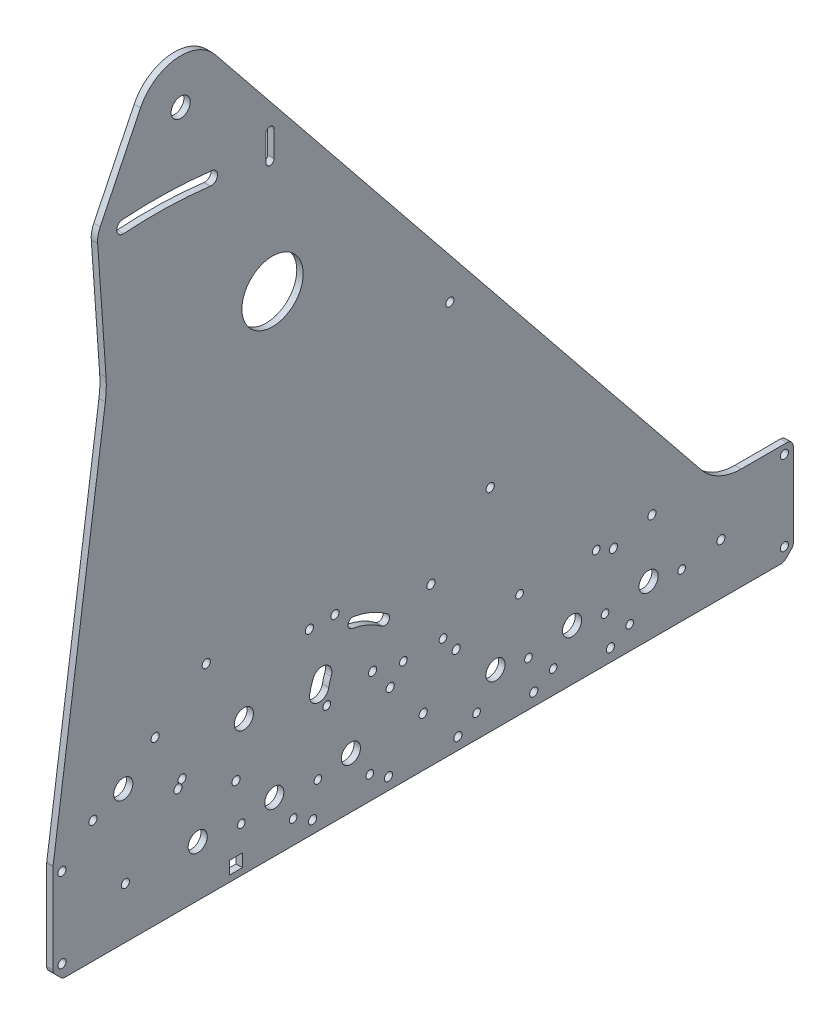
SolidWorks part; units mm, degrees
ref_plane "Front Plane" through (0, 0, 0) normal (0, 0, 1) x (1, 0, 0)
ref_plane "Top Plane" through (0, 0, 0) normal (0, 1, 0) x (1, 0, 0)
ref_plane "Right Plane" through (0, 0, 0) normal (1, 0, 0) x (0, 0, -1)
sketch "Sketch1" plane through (0, 0, 0) normal (1, 0, 0) x (0, 0, -1)
  line L0 (-184.15, -24.6062) -> (184.15, -24.6062)
  line L1 (184.15, -24.6062) -> (184.15, 26.1938)
  line L2 (184.15, 26.1938) -> (146.05, 26.1937)
  line L5 (-142.6632, 324.5299) -> (-184.15, 26.1938)
  line L6 (-184.15, 26.1938) -> (-184.15, -24.6062)
  line L7 (-184.15, 350.0437) -> (184.15, 350.0437) construction
  line L9 (146.05, 26.1937) -> (-103.3504, 335.4213)
  arc A0 (-103.3504, 335.4213) -> (-142.6632, 324.5299) centre (-120.65, 321.4687) ccw
  point P8 (0, -24.6062)
  dimension "D1" = 368.3
  dimension "D7" = 44.45
  dimension "D2" = 50.8
  dimension "D3" = 38.1
  dimension "D4" = 24.6062
  dimension "D5" = 374.65
  dimension "D6" = 304.8
  dimension "D8" = 346.075
extrude "Boss-Extrude1" add sketch "Sketch1" along normal blind 3.175
chamfer "Chamfer1" distance 4.7625 angle 45 2 edges at (1.5875, -24.6062, 184.15) (1.5875, -24.6062, -184.15)
fillet "Fillet1" radius 25.4 1 edges at (1.5875, 26.1937, -146.05)
fillet "Fillet2" radius 3.175 2 edges at (1.5875, 26.1938, 184.15) (1.5875, 26.1938, -184.15)
fillet "Fillet3" radius 3.175 4 edges at (1.5875, -19.8438, -184.15) (1.5875, -24.6062, -179.3875) (1.5875, -19.8437, 184.15) (1.5875, -24.6062, 179.3875)
sketch "Sketch30" plane through (3.175, 0, 0) normal (1, 0, 0) x (0, 0, -1)
  circle A8 centre (-89.211, 42.2593) radius 4.7625
  circle A9 centre (-25.1593, 30.6938) radius 2.032
  arc A10 (-51.7173, 35.4892) -> (-50.2741, 40.5715) centre (-25.1593, 30.6938) cw construction
  arc A11 (-54.7652, 42.3379) -> (-56.4665, 36.3468) centre (-25.1593, 30.6938) ccw
  arc A12 (-45.783, 38.8051) -> (-46.9681, 34.6317) centre (-25.1593, 30.6938) ccw
  arc A13 (-45.783, 38.8051) -> (-54.7652, 42.3379) centre (-50.2741, 40.5715) ccw
  arc A14 (-56.4665, 36.3468) -> (-46.9681, 34.6317) centre (-51.7173, 35.4892) ccw
  arc A15 (-34.9881, 56.6661) -> (-19.1131, 49.8125) centre (-41.7582, 19.1724) cw construction
  arc A16 (-17.6789, 51.753) -> (-34.5594, 59.0407) centre (-41.7582, 19.1724) ccw
  arc A17 (-20.5473, 47.8719) -> (-35.4169, 54.2915) centre (-41.7582, 19.1724) ccw
  arc A18 (-20.5473, 47.8719) -> (-17.6789, 51.753) centre (-19.1131, 49.8125) ccw
  arc A19 (-34.5594, 59.0407) -> (-35.4169, 54.2915) centre (-34.9881, 56.6661) ccw
  arc A20 (-19.1131, 49.8125) -> (-34.9881, 56.6661) centre (-41.7582, 19.1724) ccw construction
  circle A21 centre (94.6345, 23.8125) radius 2.032
  circle A22 centre (-56.6241, 64.5541) radius 2.032
  circle A23 centre (-43.9241, 64.5541) radius 2.032
  circle A24 centre (-56.6241, 64.5541) radius 1.905 construction
  circle A25 centre (-43.9241, 64.5541) radius 1.905 construction
  point P7 (-51.1204, 38.0658)
  point P19 (-26.6567, 54.1518)
  dimension "D2" = 9.652
  dimension "D4" = 4.064
  dimension "D1" = 4.064
  dimension ".375" = 9.525
  dimension "D3" = 4.826
extrude "Cut-Extrude9" cut sketch "Sketch30" against normal through all
sketch "Sketch16" plane through (3.175, 0, 0) normal (1, 0, 0) x (0, 0, -1)
  circle A0 centre (112.1746, 0.7937) radius 4.7625
  circle A1 centre (74.0746, 0.7937) radius 4.7625
  circle A2 centre (35.9746, 0.7937) radius 4.7625
  circle A3 centre (-35.9746, 0.7938) radius 4.7625
  circle A4 centre (-74.0746, 0.7938) radius 4.7625
  circle A5 centre (-112.1746, 0.7937) radius 4.7625
  dimension "D1" = 9.525
  dimension "D2" = 9.525
extrude "Cut-Extrude1" cut sketch "Sketch16" against normal up to next
sketch "Sketch25" plane through (3.175, 0, 0) normal (1, 0, 0) x (0, 0, -1)
  circle A0 centre (102.7672, -13.0003) radius 1.905 construction
  circle A1 centre (86.0486, 27.3622) radius 1.905 construction
  circle A2 centre (128.5804, -2.3081) radius 1.905 construction
  circle A3 centre (102.7672, -13.0003) radius 1.905
  circle A4 centre (86.0486, 27.3622) radius 1.905
  circle A5 centre (128.5804, -2.3081) radius 1.905
  circle A6 centre (64.6672, -13.0003) radius 1.905 construction
  circle A8 centre (-9.8486, 27.3622) radius 1.905 construction
  circle A10 centre (-47.9486, 27.3622) radius 1.905 construction
  circle A11 centre (-90.4804, -2.3081) radius 1.905 construction
  circle A12 centre (-64.6672, -13.0003) radius 1.905 construction
  circle A14 centre (-52.3804, -2.3081) radius 1.905 construction
  circle A15 centre (-26.5672, -13.0003) radius 1.905 construction
  circle A16 centre (9.8486, 27.3622) radius 1.905 construction
  circle A17 centre (26.5672, -13.0003) radius 1.905 construction
  circle A18 centre (47.9486, 27.3622) radius 1.905 construction
  circle A19 centre (52.3804, -2.3081) radius 1.905 construction
  circle A20 centre (90.4804, -2.3081) radius 1.905 construction
  circle A21 centre (-9.8486, 27.3622) radius 1.905
  circle A23 centre (-47.9486, 27.3622) radius 1.905
  circle A24 centre (-90.4804, -2.3081) radius 1.905
  circle A25 centre (-64.6672, -13.0003) radius 1.905
  circle A27 centre (-52.3804, -2.3081) radius 1.905
  circle A28 centre (-26.5672, -13.0003) radius 1.905
  circle A29 centre (9.8486, 27.3622) radius 1.905
  circle A30 centre (26.5672, -13.0003) radius 1.905
  circle A31 centre (47.9486, 27.3622) radius 1.905
  circle A32 centre (64.6672, -13.0003) radius 1.905
  circle A33 centre (52.3804, -2.3081) radius 1.905
  circle A34 centre (90.4804, -2.3081) radius 1.905
extrude "Cut-Extrude4" cut sketch "Sketch25" against normal up to next
sketch "Sketch23" plane through (3.175, 0, 0) normal (1, 0, 0) x (0, 0, -1)
  circle A0 centre (179.705, 21.7488) radius 1.905 construction
  point P0 (-55.0246, -18.3223)
  point P6 (-93.1246, 17.5943)
  point P9 (-17.2515, -18.6426)
  point P12 (-16.4124, 19.3854)
  point P15 (16.4124, 19.3854)
  point P18 (17.2515, -18.6426)
  point P21 (55.0246, -18.3223)
  point P35 (3.8736, 53.6853)
  point P38 (113.7728, 28.6594)
  point P44 (-179.705, 21.7487)
  point P47 (-179.705, -18.0026)
  point P50 (179.705, 21.7488)
  point P53 (179.705, -18.0026)
  point P59 (93.1246, -18.3223)
  point P63 (-122.0103, 28.5049)
  point P66 (-164.29, 36.0603)
hole_wizard "#8 (0.16) Diameter Hole1" positions "Sketch23" profile "Sketch24" hole size "#8" standard "ANSI Inch" end condition up to next
sketch "Sketch24" plane through (3.175, -18.3223, 55.0246) normal (0, 1, 0) x (0, 0, -1)
  line L0 (0, 0) -> (0, 3.175)
  line L1 (0, 3.175) -> (2.032, 3.175)
  line L2 (2.032, 3.175) -> (2.032, 0)
  line L5 (2.032, 0) -> (0, 0)
  line L11 (0, -6.35) -> (0, 107.95) construction
  dimension "Thru Hole Dia." = 4.064
  dimension "Thru Hole Depth" = 3.175
sketch "Sketch22" plane through (3.175, 0, 0) normal (1, 0, 0) x (0, 0, -1)
  line L0 (-96.2996, -15.1473) -> (-89.9496, -15.1473) construction
  line L1 (-96.2996, -15.1473) -> (-89.9496, -15.1473)
  line L2 (-96.2996, -15.1473) -> (-96.2996, -21.4973)
  line L3 (-96.2996, -21.4973) -> (-89.9496, -21.4973)
  line L4 (-89.9496, -15.1473) -> (-89.9496, -21.4973)
  line L5 (-96.2996, -15.1473) -> (-89.9496, -21.4973) construction
  line L6 (-96.2996, -21.4973) -> (-89.9496, -15.1473) construction
  line L7 (-89.9496, -15.1473) -> (-89.9496, -19.8734) construction
  point P0 (-93.1246, -18.3223)
  dimension "D1" = 6.35
extrude "Cut-Extrude3" cut sketch "Sketch22" against normal up to next
sketch "Sketch21" plane through (3.175, 0, 0) normal (1, 0, 0) x (0, 0, -1)
  circle A0 centre (-148.1579, 0.7937) radius 2.032
  circle A2 centre (0, 0) radius 2.032
  circle A3 centre (148.1579, 0.7938) radius 2.032
  dimension "D1" = 4.064
extrude "Cut-Extrude2" cut sketch "Sketch21" against normal up to next
sketch "Sketch26" [suppressed] plane through (3.175, 0, 0) normal (1, 0, 0) x (0, 0, -1)
  line L0 (-145.839, 321.5609) -> (-184.1236, 26.3971) construction
  line L1 (-178.0724, -24.6062) -> (178.0724, -24.6062) construction
  circle A0 centre (-121.0218, 216.6937) radius 15.24
  dimension "D1" = 30.48
  dimension "D2" = 38.1
  dimension "D3" = 241.3
extrude "Cut-Extrude5" [suppressed] cut sketch "Sketch26" against normal through all
sketch "Sketch27" plane through (3.175, 0, 0) normal (1, 0, 0) x (0, 0, -1)
  circle A0 centre (-120.65, 321.4687) radius 4.7625
  dimension "D1" = 9.525
extrude "Cut-Extrude6" cut sketch "Sketch27" against normal through all
sketch "Sketch28" plane through (3.175, 0, 0) normal (1, 0, 0) x (0, 0, -1)
  line L0 (-120.65, 321.4687) -> (-103.9389, 280.2796) construction
  line L1 (-103.9389, 280.2796) -> (-86.9156, 261.4285) construction
  line L2 (-86.9156, 261.4285) -> (-90.8226, 249.3444) construction
  line L3 (-90.8226, 249.3444) -> (-94.7296, 237.2603) construction
  line L4 (-142.6632, 324.5299) -> (-184.1197, 26.4114) construction
  circle A0 centre (-94.7296, 237.2603) radius 2.032
  circle A1 centre (-90.8226, 249.3444) radius 2.032
  circle A2 centre (-86.9156, 261.4285) radius 2.0955
  circle A3 centre (-103.9389, 280.2796) radius 2.032
  dimension "D4" = 4.064
  dimension "D5" = 4.191
  dimension "D6" = 4.064
  dimension "D1" = 25.4
  dimension "D2" = 44.45
  dimension "D3" = 12.7
  dimension "D7" = 30
  dimension "D8" = 120
  dimension "D9" = 160
extrude "Cut-Extrude7" [suppressed] cut sketch "Sketch28" against normal through all
sketch "Sketch29" plane through (3.175, 0, 0) normal (1, 0, 0) x (0, 0, -1)
  line L1 (-76.2, 288.925) -> (-76.2, 276.225) construction
  line L2 (-74.168, 288.925) -> (-74.168, 276.225)
  line L3 (-78.232, 288.925) -> (-78.232, 276.225)
  arc A4 (-74.168, 288.925) -> (-78.232, 288.925) centre (-76.2, 288.925) ccw
  arc A5 (-78.232, 276.225) -> (-74.168, 276.225) centre (-76.2, 276.225) ccw
  point P8 (-76.2, 282.575)
  dimension "D1" = 276.225
  dimension "D2" = 2.032
  dimension "D3" = 76.2
  dimension "D4" = 12.7
sketch "Sketch31" plane through (0, 0, 0) normal (-1, 0, 0) x (0, 0, 1)
extrude "Cut-Extrude10" [suppressed] cut sketch "Sketch31" against normal through all
sketch "Sketch34" plane through (0, 0, 0) normal (-1, 0, 0) x (0, 0, 1)
  line L3 (123.2042, 95.6381) -> (126.7027, 70.4802) construction
  line L4 (125.3426, 95.9355) -> (128.8411, 70.7775)
  line L5 (121.0658, 95.3407) -> (124.5642, 70.1828)
  line L6 (142.6632, 324.5299) -> (184.1197, 26.4114) construction
  arc A2 (125.3426, 95.9355) -> (121.0658, 95.3407) centre (123.2042, 95.6381) ccw
  arc A3 (124.5642, 70.1828) -> (128.8411, 70.7775) centre (126.7027, 70.4802) ccw
  point P9 (124.9534, 83.0591)
  dimension "D8" = 4.318
  dimension "D6" = 50.8
  dimension "D7" = 25.4
extrude "Cut-Extrude12" [suppressed] cut sketch "Sketch34" against normal through all
sketch "Sketch38" plane through (3.175, 0, 0) normal (1, 0, 0) x (0, 0, -1)
  line L0 (-184.15, 25.974) -> (-184.15, -18.5286) construction
  line L1 (-178.0724, -24.6062) -> (178.0724, -24.6062) construction
  circle A0 centre (-133.35, 56.3562) radius 2.032
  circle A1 centre (-149.225, 42.0687) radius 4.7625
  circle A2 centre (-107.95, 75.4062) radius 2.032
  dimension "D1" = 50.8
  dimension "D3" = 4.064
  dimension "D4" = 9.525
  dimension "D7" = 4.064
  dimension "D2" = 80.9625
  dimension "D5" = 15.875
  dimension "D6" = 14.2875
  dimension "D8" = 25.4
  dimension "D9" = 19.05
extrude "Cut-Extrude14" cut sketch "Sketch38" against normal through all
sketch "Sketch37" plane through (3.175, 0, 0) normal (1, 0, 0) x (0, 0, -1)
  circle A0 centre (33.3375, 80.645) radius 2.032
  circle A8 centre (0, 0) radius 2.032 construction
  dimension "D1" = 4.064
  dimension "D2" = 33.3375
  dimension "D3" = 80.645
extrude "Cut-Extrude13" cut sketch "Sketch37" against normal through all
extrude "Cut-Extrude15" cut sketch "Sketch29" against normal through all
sketch "Sketch40" plane through (3.175, 0, 0) normal (1, 0, 0) x (0, 0, -1)
  circle A0 centre (-120.015, 31.75) radius 2.032
  dimension "D1" = 4.064
  dimension "D2" = 120.015
  dimension "D3" = 31.75
extrude "Cut-Extrude16" cut sketch "Sketch40" against normal through all
sketch "Sketch41" [suppressed] plane through (3.175, 0, 0) normal (1, 0, 0) x (0, 0, -1)
  line L0 (-120.65, 318.2937) -> (-98.425, 279.7989) construction
  line L1 (-98.425, 279.7989) -> (-77.6666, 265.1617) construction
  line L2 (-120.65, 318.2937) -> (-60.41, 318.2937) construction
  circle A0 centre (-120.65, 318.2937) radius 25.4 construction
  circle A1 centre (-98.425, 279.7989) radius 19.05 construction
  circle A2 centre (-77.6666, 265.1617) radius 6.35 construction
  circle A3 centre (-98.425, 279.7989) radius 2.032
  circle A4 centre (-77.6666, 265.1617) radius 2.032
  dimension "D1" = 50.8
  dimension "D2" = 38.1
  dimension "D3" = 12.7
  dimension "D4" = 4.064
  dimension "D5" = 60
extrude "Cut-Extrude17" [suppressed] cut sketch "Sketch41" against normal through all
sketch "Sketch43" plane through (3.175, 0, 0) normal (1, 0, 0) x (0, 0, -1)
  line L0 (-152.4, 200.025) -> (-123.6487, 200.025) construction
  line L1 (-115.9779, 252.0412) -> (-152.4, 200.025) construction
  circle A0 centre (-152.4, 200.025) radius 2.032
  arc A1 (-143.2813, 262.8669) -> (-96.4668, 230.087) centre (-152.4, 200.025) cw construction
  arc A2 (-92.2158, 232.3717) -> (-142.5883, 267.6428) centre (-152.4, 200.025) ccw
  arc A3 (-100.7177, 227.8023) -> (-143.9743, 258.0909) centre (-152.4, 200.025) ccw
  arc A4 (-100.7177, 227.8023) -> (-92.2158, 232.3717) centre (-96.4668, 230.087) ccw
  arc A5 (-142.5883, 267.6428) -> (-143.9743, 258.0909) centre (-143.2813, 262.8669) ccw
  point P6 (-115.9779, 252.0412)
  dimension "D1" = 4.064
  dimension "D4" = 4.826
  dimension "D2" = 200.025
  dimension "D3" = 152.4
  dimension "D5" = 63.5
  dimension "D6" = 57.15
  dimension "D7" = 55
extrude "Cut-Extrude19" [suppressed] cut sketch "Sketch43" against normal through all
sketch "Sketch44" plane through (3.175, 0, 0) normal (1, 0, 0) x (0, 0, -1)
  circle A0 centre (-142.875, 226.3775) radius 2.032
  dimension "D1" = 4.064
  dimension "D2" = 142.875
  dimension "D3" = 226.3775
extrude "Cut-Extrude20" [suppressed] cut sketch "Sketch44" against normal through all
sketch "Sketch50" plane through (0, 0, 0) normal (-1, 0, 0) x (0, 0, 1)
  line L0 (89.6567, 207.1688) -> (64.2567, 207.1688) construction
  line L1 (89.6567, 205.1368) -> (64.2567, 205.1368)
  line L2 (89.6567, 209.2008) -> (64.2567, 209.2008)
  line L3 (64.2567, 194.4688) -> (38.8567, 194.4688) construction
  line L4 (64.2567, 192.4368) -> (38.8567, 192.4368)
  line L5 (64.2567, 196.5008) -> (38.8567, 196.5008)
  arc A1 (89.6567, 205.1368) -> (89.6567, 209.2008) centre (89.6567, 207.1688) ccw
  arc A2 (64.2567, 209.2008) -> (64.2567, 205.1368) centre (64.2567, 207.1688) ccw
  arc A3 (64.2567, 192.4368) -> (64.2567, 196.5008) centre (64.2567, 194.4688) ccw
  arc A4 (38.8567, 196.5008) -> (38.8567, 192.4368) centre (38.8567, 194.4688) ccw
  point P3 (76.9567, 207.1688)
  point P5 (51.5567, 194.4688)
  dimension "D1" = 2.032
  dimension "D2" = 207.1688
  dimension "D3" = 89.6567
  dimension "D4" = 25.4
  dimension "D5" = 12.7
extrude "Cut-Extrude22" [suppressed] cut sketch "Sketch50" against normal through all
sketch "Sketch51" plane through (3.175, 0, 0) normal (1, 0, 0) x (0, 0, -1)
  circle A0 centre (-111.125, 222.6469) radius 2.032
  circle A1 centre (-111.125, 190.8969) radius 2.032
  dimension "D1" = 222.6469
  dimension "D3" = 31.75
  dimension "D4" = 4.064
  dimension "D2" = 111.125
extrude "Cut-Extrude23" [suppressed] cut sketch "Sketch51" against normal through all
sketch "Sketch52" [suppressed] plane through (0, 0, 0) normal (-1, 0, 0) x (0, 0, 1)
  line L0 (145.839, 321.5609) -> (184.1236, 26.3971) construction
  line L1 (142.875, 226.3775) -> (142.0856, 251.7652) construction
  line L2 (120.4939, 238.3877) -> (142.875, 226.3775) construction
  arc A5 (142.0856, 251.7652) -> (120.4939, 238.3877) centre (142.875, 226.3775) ccw construction
  arc A6 (142.0224, 253.7962) -> (118.7034, 239.3485) centre (142.875, 226.3775) ccw
  arc A7 (142.1487, 249.7342) -> (122.2844, 237.4269) centre (142.875, 226.3775) ccw
  arc A8 (142.1487, 249.7342) -> (142.0224, 253.7962) centre (142.0856, 251.7652) ccw
  arc A9 (118.7034, 239.3485) -> (122.2844, 237.4269) centre (120.4939, 238.3877) ccw
  point P4 (129.4975, 247.9692)
  dimension "D1" = 25.4
  dimension "D2" = 2.032
  dimension "D3" = 12.7
  dimension "D4" = 60
extrude "Cut-Extrude24" [suppressed] cut sketch "Sketch52" against normal through all
sketch "Sketch53" plane through (3.175, 0, 0) normal (1, 0, 0) x (0, 0, -1)
  line L0 (-25.4, 197.2663) -> (-25.4, 135.876) construction
  line L1 (-23.368, 197.2663) -> (-23.368, 135.876)
  line L2 (-27.432, 197.2663) -> (-27.432, 135.876)
  arc A0 (-23.368, 197.2663) -> (-27.432, 197.2663) centre (-25.4, 197.2663) ccw
  arc A1 (-27.432, 135.876) -> (-23.368, 135.876) centre (-25.4, 135.876) ccw
  point P2 (-25.4, 166.5712)
  dimension "D1" = 2.032
  dimension "D2" = 61.3903
  dimension "D3" = 197.2663
  dimension "D4" = 25.4
extrude "Cut-Extrude25" [suppressed] cut sketch "Sketch53" against normal through all
sketch "Sketch56" plane through (3.175, 0, 0) normal (1, 0, 0) x (0, 0, -1)
  line L0 (-133.35, 284.9563) -> (-133.35, 56.3562) construction
  line L1 (-149.2963, 284.3994) -> (-133.35, 56.3562) construction
  line L2 (-133.35, 56.3562) -> (-105.4907, 283.2523) construction
  arc A0 (-149.2963, 284.3994) -> (-105.4907, 283.2523) centre (-133.35, 56.3562) cw
  arc A1 (-142.7671, 191.0274) -> (-116.8976, 190.35) centre (-133.35, 56.3562) cw
  dimension "D1" = 4
  dimension "D3" = 228.6
  dimension "D4" = 135
  dimension "D2" = 7
sketch "Sketch54" plane through (3.175, 0, 0) normal (1, 0, 0) x (0, 0, -1)
  line L0 (-142.6632, 324.5299) -> (-184.1197, 26.4114) construction
  line L1 (-140.6316, 331.1994) -> (-160.7144, 289.9597)
  line L2 (-142.6632, 324.5299) -> (-157.4154, 218.4453)
  line L3 (-140.6316, 331.1994) -> (-217.348, 331.1994) construction
  line L4 (-149.2963, 284.3994) -> (-133.35, 56.3562) construction
  line L5 (-161.9654, 283.5135) -> (-157.4154, 218.4453)
  arc A1 (-103.3504, 335.4213) -> (-142.6632, 324.5299) centre (-120.65, 321.4687) ccw construction
  arc A2 (-160.7144, 289.9597) -> (-161.9654, 283.5135) centre (-149.2963, 284.3994) ccw
  arc A3 (-140.6316, 331.1994) -> (-142.6632, 324.5299) centre (-120.65, 321.4687) ccw
  dimension "D1" = 12.7
extrude "Boss-Extrude2" add sketch "Sketch54" against normal up to surface (3.175 mm away) up to face at (0, 282.575, 76.2)
sketch "Sketch57" plane through (3.175, 0, 0) normal (1, 0, 0) x (0, 0, -1)
  line L0 (138.4249, 35.6479) -> (-103.3504, 335.4213) construction
  arc A0 (-149.2963, 284.3994) -> (-105.4907, 283.2523) centre (-133.35, 56.3562) cw construction
  arc A1 (-105.1037, 286.4036) -> (-149.5178, 287.5667) centre (-133.35, 56.3562) ccw
  arc A2 (-105.8776, 280.101) -> (-149.0749, 281.2321) centre (-133.35, 56.3562) ccw
  arc A3 (-105.8776, 280.101) -> (-105.1037, 286.4036) centre (-105.4907, 283.2523) ccw
  arc A4 (-149.5178, 287.5667) -> (-149.0749, 281.2321) centre (-149.2963, 284.3994) ccw
  arc A5 (-105.4907, 283.2523) -> (-149.2963, 284.3994) centre (-133.35, 56.3562) ccw construction
  arc A6 (-142.7671, 191.0274) -> (-116.8976, 190.35) centre (-133.35, 56.3562) cw construction
  arc A7 (-116.5107, 193.5013) -> (-142.9886, 194.1947) centre (-133.35, 56.3562) ccw construction
  arc A8 (-117.2846, 187.1986) -> (-142.5456, 187.8601) centre (-133.35, 56.3562) ccw construction
  arc A9 (-117.2846, 187.1986) -> (-116.5107, 193.5013) centre (-116.8976, 190.35) ccw construction
  arc A10 (-142.9886, 194.1947) -> (-142.5456, 187.8601) centre (-142.7671, 191.0274) ccw construction
  circle A11 centre (13.2774, 170.5867) radius 2.032
  point P3 (-127.3659, 284.8779)
  point P16 (-129.8161, 191.31)
  dimension "D1" = 6.35
  dimension "D2" = 4.064
  dimension "D3" = 12.7
  dimension "D4" = 130.175
extrude "Cut-Extrude26" cut sketch "Sketch57" against normal up to next
sketch "Sketch58" plane through (3.175, 0, 0) normal (1, 0, 0) x (0, 0, -1)
  line L0 (138.4249, 35.6479) -> (-103.3504, 335.4213) construction
  line L1 (-74.9571, 219.298) -> (-112.7732, 223.9412) construction
  line L2 (-133.35, 56.3562) -> (-105.4907, 283.2523) construction
  circle A0 centre (-74.9571, 219.298) radius 15.24
  dimension "D1" = 50.8
  dimension "D2" = 30.48
  dimension "D3" = 38.1
extrude "Cut-Extrude27" cut sketch "Sketch58" against normal through all
sketch "Sketch60" [suppressed] plane through (0, 0, 0) normal (-1, 0, 0) x (0, 0, 1)
  line L1 (-40.2733, 127) -> (106.3603, 186.4422) construction
  line L2 (120.65, 321.4687) -> (120.65, 283.4951) construction
  line L3 (-40.2733, 127) -> (67.2673, 265.0656) construction
  line L4 (109.8203, 191.9056) -> (104.0156, 294.388) construction
  line L5 (69.0152, 266.5427) -> (112.1985, 289.8108) construction
  line L6 (-138.4249, 35.6479) -> (103.3504, 335.4213) construction
  line L7 (120.65, 321.4687) -> (120.65, 359.4144) construction
  line L8 (120.65, 321.4687) -> (109.5629, 294.7022) construction
  line L10 (120.65, 321.4687) -> (-169.232, 227.2804) construction
  line L11 (120.65, 321.4687) -> (354.1403, 125.5471) construction
  circle A7 centre (74.8099, 220.4974) radius 33.3375 construction
  circle A10 centre (71.6507, 261.6513) radius 2.032
  circle A11 centre (71.6507, 261.6513) radius 7.9375 construction
  circle A12 centre (104.2729, 191.5914) radius 2.032
  circle A14 centre (104.2729, 191.5914) radius 7.9375 construction
  circle A15 centre (-40.2733, 127) radius 2.032
  circle A16 centre (104.2729, 191.5914) radius 5.5563 construction
  circle A17 centre (120.65, 321.4687) radius 22.225 construction
  circle A20 centre (109.5629, 294.7022) radius 6.7469 construction
  circle A21 centre (109.5629, 294.7022) radius 2.032
  circle A22 centre (109.5629, 294.7022) radius 5.5563 construction
  circle A23 centre (71.6507, 261.6513) radius 5.5563 construction
  dimension "D4" = 11.1125
  dimension "D3" = 13.4937
  dimension "D6" = 66.675
  dimension "D7" = 4.064
  dimension "D8" = 19.05
  dimension "D2" = 22.5
  dimension "D9" = 15.875
  dimension "D5" = 44.45
  dimension "D10" = 127
  dimension "D11" = 108
  dimension "D12" = 130
  dimension "D13" = 304.8
  dimension "D14" = 304.8
extrude "Cut-Extrude28" [suppressed] cut sketch "Sketch60" against normal through all
fillet "Fillet4" radius 50.8 1 edges at (1.5875, 218.4453, 157.4154)
